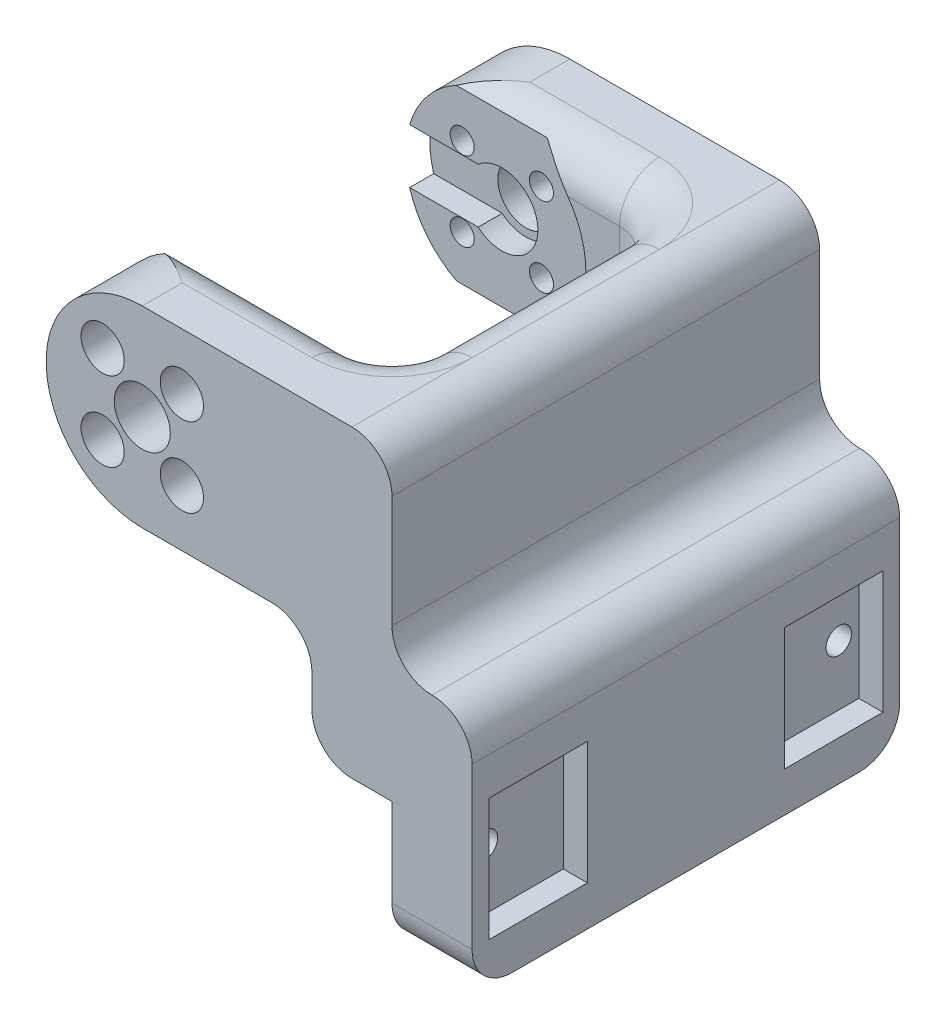
SolidWorks part; units mm, degrees
ref_plane "前视基准面" through (0, 0, 0) normal (0, 0, 1) x (1, 0, 0)
ref_plane "上视基准面" through (0, 0, 0) normal (0, 1, 0) x (1, 0, 0)
ref_plane "右视基准面" through (0, 0, 0) normal (1, 0, 0) x (0, 0, -1)
other "Configuration Table"
sketch "草图1" plane through (0, 0, 0) normal (0, 0, 1) x (1, 0, 0)
  line L0 (0, 12) -> (36.1853, 12)
  line L1 (36.1853, 12) -> (36.1853, -12)
  line L2 (36.1853, -12) -> (0, -12)
  arc A0 (0, 12) -> (0, -12) centre (0, 0) ccw
  dimension "D1" = 36.1853
extrude "凸台-拉伸1" add sketch "草图1" along normal blind 13.5
ref_plane "基准面1" through (0, 0, -16.7) normal (0, 0, -1) x (-1, 0, 0)
sketch "草图5" plane through (0, 0, 0) normal (0, 0, -1) x (-1, 0, 0)
  circle A0 centre (0, 0) radius 10.1
extrude "切除-拉伸2" cut sketch "草图5" against normal blind 1.5
sketch "草图7" plane through (0, 0, 1.5) normal (0, 0, -1) x (-1, 0, 0)
  circle A0 centre (0, 0) radius 3.5
extrude "切除-拉伸3" cut sketch "草图7" against normal blind 37
sketch "草图35" plane through (0, 0, 1.5) normal (0, 0, -1) x (-1, 0, 0)
  circle A0 centre (0, 0) radius 4.5
extrude "切除-拉伸22" cut sketch "草图35" against normal blind 3
sketch "草图9" plane through (0, 0, 1.5) normal (0, 0, -1) x (-1, 0, 0)
  line L0 (-4.9497, 4.9497) -> (0, 0) construction
  line L1 (0, 0) -> (0, 7.7766) construction
  circle A0 centre (-4.9497, 4.9497) radius 1.5
  circle A1 centre (4.9497, 4.9497) radius 1.5
  circle A2 centre (4.9497, -4.9497) radius 1.5
  circle A3 centre (-4.9497, -4.9497) radius 1.5
  point P14 (0, 0)
  dimension "D1" = 7
  dimension "D2" = 45
  dimension "D3" = 4
extrude "切除-拉伸4" cut sketch "草图9" against normal blind 24.5
mirror "镜向14" about plane through (0, 0, -16.7) normal (0, 0, -1) of bodies 111
sketch "草图11" plane through (36.1853, 0, 0) normal (1, 0, 0) x (0, 0, -1)
  line L1 (-13.5, 12) -> (46.9, 12)
  line L2 (-13.5, 12) -> (-13.5, -12)
  line L3 (-13.5, -12) -> (46.9, -12)
  line L4 (46.9, 12) -> (46.9, -12)
extrude "凸台-拉伸2" add sketch "草图11" against normal blind 10
sketch "草图12" plane through (0, 0, 13.5) normal (0, 0, 1) x (1, 0, 0)
  circle A0 centre (4.9497, 4.9497) radius 2.7
  circle A1 centre (4.9497, -4.9497) radius 2.7
  circle A2 centre (-4.9497, -4.9497) radius 2.7
  circle A3 centre (-4.9497, 4.9497) radius 2.7
  point P12 (0, 0)
  dimension "D1" = 4
extrude "切除-拉伸5" cut sketch "草图12" against normal blind 8.5
sketch "草图18" plane through (0, 0, 0) normal (0, 0, -1) x (-1, 0, 0)
  circle A0 centre (0, 0) radius 12
extrude "切除-拉伸9" cut sketch "草图18" against normal blind 1.5
sketch "草图19" plane through (0, 0, 1.5) normal (0, 0, -1) x (-1, 0, 0)
  line L4 (0, 0) -> (8.3144, 0) construction
  line L5 (16.6287, -3.4) -> (0, -3.4)
  line L6 (16.6287, -3.4) -> (16.6287, 3.4)
  line L7 (16.6287, 3.4) -> (0, 3.4)
  line L8 (0, -3.4) -> (0, 3.4)
  line L9 (16.6287, -3.4) -> (0, 3.4) construction
  line L10 (16.6287, 3.4) -> (0, -3.4) construction
  point P0 (8.3144, 0)
  dimension "D1" = 6.8
extrude "切除-拉伸10" cut sketch "草图19" against normal blind 3
sketch "草图20" plane through (0, 0, 13.5) normal (0, 0, 1) x (1, 0, 0)
  line L1 (-17.9701, 18.7991) -> (58.5374, 18.7991)
  line L2 (-17.9701, 18.7991) -> (-17.9701, -18.303)
  line L3 (-17.9701, -18.303) -> (58.5374, -18.303)
  line L4 (58.5374, 18.7991) -> (58.5374, -18.303)
extrude "切除-拉伸11" cut sketch "草图20" against normal blind 3.5
mirror "镜向24" about plane through (0, 0, -16.7) normal (0, 0, -1) of "切除-拉伸5", "切除-拉伸9", "切除-拉伸10"
mirror "镜向26" about plane through (0, 0, -16.7) normal (0, 0, -1) of "切除-拉伸11"
sketch "草图21" plane through (0, -12, 0) normal (0, -1, 0) x (1, 0, 0)
  line L0 (0, 10) -> (36.1853, 10) construction
  line L1 (26.1853, 10) -> (36.1853, 10)
  line L2 (26.1853, 10) -> (26.1853, -43.4)
  line L3 (26.1853, -43.4) -> (36.1853, -43.4)
  line L4 (36.1853, 10) -> (36.1853, -43.4)
  line L5 (26.1853, 0) -> (26.1853, -33.4) construction
  dimension "D1" = 0
extrude "凸台-拉伸3" add sketch "草图21" along normal blind 30
sketch "草图22" plane through (36.1853, 0, 0) normal (1, 0, 0) x (0, 0, -1)
  line L0 (43.4, 12) -> (43.4, -42) construction
  line L1 (-10, -42) -> (43.4, -42)
  line L2 (-10, -42) -> (-10, 12)
  line L3 (-10, 12) -> (43.4, 12)
  line L4 (43.4, -42) -> (43.4, 12)
  line L5 (-10, 12) -> (43.4, 12) construction
  dimension "D1" = 0
extrude "凸台-拉伸4" add sketch "草图22" along normal blind 15
sketch "草图24" plane through (51.1853, 0, 0) normal (1, 0, 0) x (0, 0, -1)
  line L0 (-10, -42) -> (43.4, -42) construction
  line L1 (29, -21.7) -> (41.3, -21.7)
  line L2 (29, -21.7) -> (29, -37)
  line L3 (29, -37) -> (41.3, -37)
  line L4 (41.3, -21.7) -> (41.3, -37)
  line L5 (16.7, -13.2) -> (16.7, 13.2) construction
  line L6 (4.4, -37) -> (-7.9, -37)
  line L7 (-7.9, -21.7) -> (-7.9, -37)
  line L8 (4.4, -21.7) -> (-7.9, -21.7)
  line L9 (4.4, -21.7) -> (4.4, -37)
  dimension "D1" = 15.3
  dimension "D2" = 12.3
  dimension "D3" = 5
  dimension "D4" = 12.3
extrude "切除-拉伸12" cut sketch "草图24" against normal blind 3
sketch "草图25" plane through (26.1853, 0, 0) normal (-1, 0, 0) x (0, 0, 1)
  line L0 (10, -42) -> (10, -12) construction
  line L5 (-43.4, -42) -> (10, -42)
  line L6 (-43.4, -42) -> (-43.4, -26)
  line L7 (-43.4, -26) -> (10, -26)
  line L8 (10, -42) -> (10, -26)
  dimension "D1" = 16
sketch "草图26" plane through (48.1853, 0, 0) normal (1, 0, 0) x (0, 0, -1)
  line L0 (29, -37) -> (41.3, -37) construction
  line L2 (41.3, -37) -> (41.3, -21.7) construction
  line L3 (16.7, -13.2) -> (16.7, 13.2) construction
  circle A0 centre (38.8, -29.5) radius 1.6
  circle A1 centre (-5.4, -29.5) radius 1.6
  dimension "D1" = 7.5
  dimension "D2" = 2.5
extrude "切除-拉伸14" cut sketch "草图26" against normal blind 15
sketch "草图27" plane through (0, 12, 0) normal (0, 1, 0) x (1, 0, 0)
  line L11 (0, 43.4) -> (51.1853, 43.4) construction
  line L12 (36.1853, 43.4) -> (51.1853, 43.4)
  line L13 (36.1853, 43.4) -> (36.1853, -10)
  line L14 (36.1853, -10) -> (51.1853, -10)
  line L15 (51.1853, 43.4) -> (51.1853, -10)
  dimension "D1" = 15
extrude "切除-拉伸15" cut sketch "草图27" against normal up to surface (24 mm away) up to face at (10.4741, -12, -37.7)
extrude "切除-拉伸16" cut sketch "草图25" against normal blind 15
sketch "草图28" plane through (41.1853, 0, 0) normal (-1, 0, 0) x (0, 0, 1)
  line L4 (-43.4, -26) -> (-43.4, -42)
  line L5 (-43.4, -42) -> (10, -42)
  line L6 (10, -42) -> (10, -26)
  line L7 (10, -26) -> (-43.4, -26)
  line L8 (-43.4, -26) -> (-43.4, -42)
  line L9 (-43.4, -42) -> (10, -42)
  line L10 (10, -42) -> (10, -26)
  line L11 (10, -26) -> (-43.4, -26)
  circle A0 centre (5.4, -29.5) radius 1.6 construction
  circle A1 centre (-38.8, -29.5) radius 1.6 construction
  circle A2 centre (5.4, -29.5) radius 1.6
  circle A3 centre (-38.8, -29.5) radius 1.6
  dimension "D1" = 0
extrude "凸台-拉伸5" add sketch "草图28" along normal blind 10
sketch "草图29" plane through (48.1853, 0, 0) normal (1, 0, 0) x (0, 0, -1)
  line L0 (4.4, -37) -> (4.4, -21.7) construction
  line L1 (4.4, -21.7) -> (-7.9, -21.7) construction
  line L2 (-7.9, -21.7) -> (-7.9, -37) construction
  line L3 (-7.9, -37) -> (4.4, -37) construction
  line L4 (29, -21.7) -> (29, -37) construction
  line L5 (29, -37) -> (41.3, -37) construction
  line L6 (41.3, -37) -> (41.3, -21.7) construction
  line L7 (41.3, -21.7) -> (29, -21.7) construction
  line L8 (4.4, -37) -> (4.4, -21.7)
  line L9 (4.4, -21.7) -> (-7.9, -21.7)
  line L10 (-7.9, -21.7) -> (-7.9, -37)
  line L11 (-7.9, -37) -> (4.4, -37)
  line L12 (29, -21.7) -> (29, -37)
  line L13 (29, -37) -> (41.3, -37)
  line L14 (41.3, -37) -> (41.3, -21.7)
  line L15 (41.3, -21.7) -> (29, -21.7)
  circle A0 centre (38.8, -29.5) radius 1.6 construction
  circle A1 centre (-5.4, -29.5) radius 1.6 construction
  circle A2 centre (38.8, -29.5) radius 1.6
  circle A3 centre (-5.4, -29.5) radius 1.6
extrude "切除-拉伸17" cut sketch "草图29" against normal blind 10
sketch "草图30" plane through (51.1853, 0, 0) normal (1, 0, 0) x (0, 0, -1)
  line L4 (43.4, -12) -> (-10, -12)
  line L5 (-10, -12) -> (-10, -42)
  line L6 (-10, -42) -> (43.4, -42)
  line L7 (43.4, -42) -> (43.4, -12)
  line L8 (43.4, -12) -> (-10, -12)
  line L9 (-10, -12) -> (-10, -42)
  line L10 (-10, -42) -> (43.4, -42)
  line L11 (43.4, -42) -> (43.4, -12)
  dimension "D1" = 0
extrude "切除-拉伸18" cut sketch "草图30" against normal blind 10
sketch "草图31" plane through (26.1853, 0, 0) normal (-1, 0, 0) x (0, 0, 1)
  line L8 (-43.4, -12) -> (-43.4, -26)
  line L9 (-43.4, -26) -> (10, -26)
  line L10 (10, -26) -> (10, -12)
  line L11 (10, -12) -> (0, -12)
  line L12 (0, -12) -> (0, 12)
  line L13 (0, 12) -> (-33.4, 12)
  line L14 (-33.4, 12) -> (-33.4, -12)
  line L15 (-33.4, -12) -> (-43.4, -12)
  line L16 (-43.4, -12) -> (-43.4, -26)
  line L17 (-43.4, -26) -> (10, -26)
  line L18 (10, -26) -> (10, -12)
  line L19 (10, -12) -> (0, -12)
  line L20 (0, -12) -> (0, 12)
  line L21 (0, 12) -> (-33.4, 12)
  line L22 (-33.4, 12) -> (-33.4, -12)
  line L23 (-33.4, -12) -> (-43.4, -12)
  dimension "D1" = 0
extrude "凸台-拉伸6" add sketch "草图31" along normal blind 5
sketch "草图32" plane through (36.1853, 0, 0) normal (1, 0, 0) x (0, 0, -1)
  line L4 (-10, -12) -> (43.4, -12)
  line L5 (43.4, -12) -> (43.4, 12)
  line L6 (43.4, 12) -> (-10, 12)
  line L7 (-10, 12) -> (-10, -12)
  line L8 (-10, -12) -> (43.4, -12)
  line L9 (43.4, -12) -> (43.4, 12)
  line L10 (43.4, 12) -> (-10, 12)
  line L11 (-10, 12) -> (-10, -12)
  dimension "D1" = 0
extrude "切除-拉伸19" cut sketch "草图32" against normal blind 5
fillet "圆角7" radius 5 9 edges at (21.1853, -12, -38.4) (21.1853, 12, -16.7) (21.1853, -12, 5) (10.5927, 12, -33.4) (21.1853, 0, -33.4) (10.5927, -12, -33.4) (10.5927, 12, 0) (21.1853, 0, 0) (10.5927, -12, 0)
fillet "圆角8" radius 5 3 edges at (31.1853, 12, -16.7) (31.1853, -12, -16.7) (21.1853, -26, -16.7)
fillet "圆角9" radius 5 2 edges at (36.1853, -42, 10) (36.1853, -42, -43.4)
fillet "圆角10" radius 5 1 edges at (41.1853, -12, -16.7)
